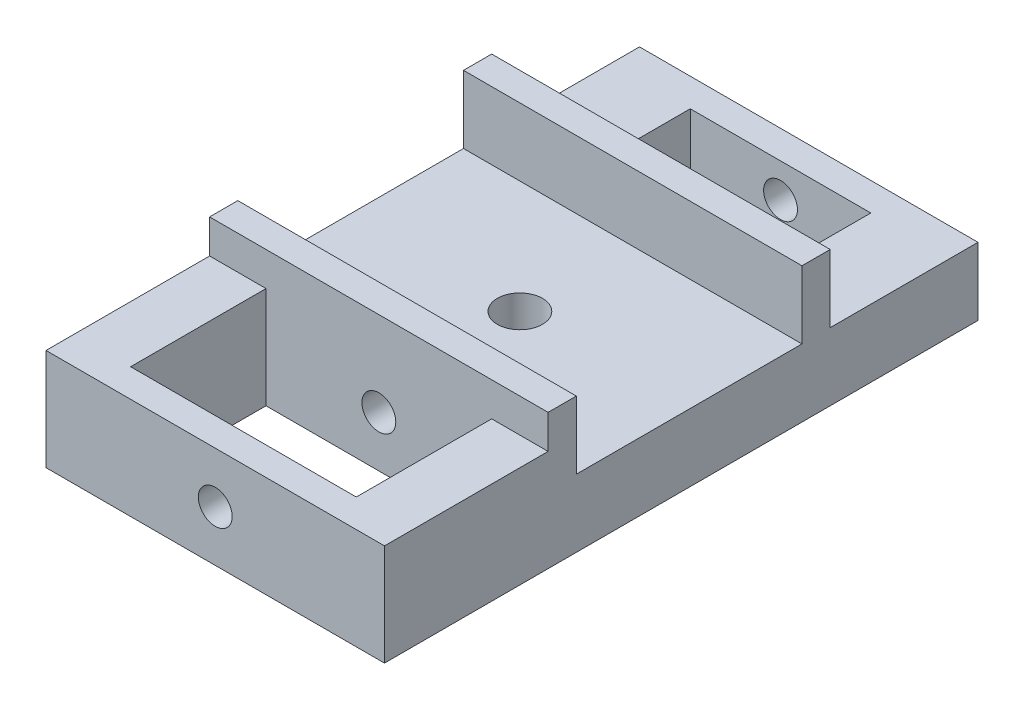
SolidWorks part; units mm, degrees
ref_plane "Front" through (0, 0, 0) normal (0, 0, 1) x (1, 0, 0)
ref_plane "Top" through (0, 0, 0) normal (0, 1, 0) x (1, 0, 0)
ref_plane "Right" through (0, 0, 0) normal (1, 0, 0) x (0, 0, -1)
sketch "Sketch1" plane through (0, 0, 0) normal (0, 1, 0) x (1, 0, 0)
  line L0 (0, -20) -> (0, -22.5)
  line L1 (0, 0) -> (-30, 0)
  line L2 (0, 0) -> (0, -20)
  line L3 (0, -20) -> (-30, -20)
  line L4 (-30, 0) -> (-30, -20)
  line L5 (0, -22.5) -> (-30, -22.5)
  line L6 (-30, -22.5) -> (-30, -20)
  line L7 (0, 0) -> (-7, 0)
  line L8 (-30, 0) -> (0, 0)
  line L9 (-30, 0) -> (-30, 2.5)
  line L10 (-30, 2.5) -> (0, 2.5)
  line L11 (0, 0) -> (0, 2.5)
  line L12 (-30, 0) -> (-23, 0)
  line L13 (-30, 2.5) -> (-30, 13.1)
  line L14 (-30, 13.1) -> (0, 13.1)
  line L15 (0, 13.1) -> (0, 2.5)
  line L16 (0, 13.1) -> (0, 15.6)
  line L17 (0, 15.6) -> (-30, 15.6)
  line L18 (-30, 15.6) -> (-30, 13.1)
  line L19 (-7, 0) -> (-7, 15.6)
  line L20 (-23, 0) -> (-23, 15.6)
  dimension "D1" = 20
  dimension "D2" = 2.5
  dimension "D3" = 2.5
  dimension "D4" = 30
  dimension "D5" = 7
  dimension "D6" = 7
  dimension "D7" = 10.6
  dimension "D8" = 2.5
extrude "Boss-Extrude1" add sketch "Sketch1" along normal blind 6 contours L1 L8 L4 L3 L2 | L6 L5 L0 L3 | L20 L1 L19 L10 | L19 L1 L11 L10 | L19 L10 L15 L14 | L19 L14 L16 L17 | L20 L14 L19 L17 | L14 L20 L17 L18 | L10 L20 L14 L13 | L8 L20 L10 L9 region at (-15, 0, 10) region at (-15, 0, 21.25) region at (-3.5, 0, -1.25) region at (-15, 0, -1.25) region at (-3.5, 0, -7.8) region at (-26.5, 0, -1.25) region at (-3.5, 0, -14.35) region at (-26.5, 0, -7.8) region at (-15, 0, -14.35) region at (-26.5, 0, -14.35)
extrude "Boss-Extrude2" add sketch "Sketch1<3>" along normal blind 12 contours L19 L1 L11 L10 | L20 L1 L19 L10 | L6 L5 L0 L3 | L8 L20 L10 L9 region at (-15, 0, 21.25) region at (-3.5, 0, -1.25) region at (-15, 0, -1.25) region at (-26.5, 0, -1.25)
sketch "Sketch1<3>" plane through (0, 0, 0) normal (0, 1, 0) x (1, 0, 0) same geometry as "Sketch1"
sketch "Sketch3" plane through (0, 0, -15.6) normal (0, 0, -1) x (-1, 0, 0)
  line L0 (30, 3) -> (23, 3)
  line L1 (30, 6) -> (30, 0) construction
  line L2 (23, 3) -> (15, 3)
  circle A0 centre (15, 3) radius 1.5
  dimension "D1" = 7
  dimension "D2" = 8
extrude "Cut-Extrude2" cut sketch "Sketch3" against normal blind 16 contours A0
ref_plane "Plane1" through (0, 0, 10) normal (0, 0, -1) x (-1, 0, 0)
sketch "Sketch2" plane through (0, 6, 0) normal (0, 1, 0) x (1, 0, 0)
  line L0 (-30, -10) -> (0, -10)
  line L1 (-30, 0) -> (-30, -20) construction
  line L2 (0, 0) -> (0, -20) construction
  circle A0 centre (-15, -10) radius 2
extrude "Cut-Extrude1" cut sketch "Sketch2" against normal through all contours L0 A0 | L0 A0 region at (-15, 6, 9.1512) region at (-15, 6, 10.8488)
sketch "Sketch5" plane through (0, 0, 0) normal (0, -1, 0) x (1, 0, 0)
  line L0 (-30, 22.5) -> (-25, 22.5)
  line L1 (-30, 22.5) -> (0, 22.5)
  line L2 (-30, 22.5) -> (-30, 34.5)
  line L3 (0, 22.5) -> (0, 34.5)
  line L4 (-30, 34.5) -> (0, 34.5)
  line L5 (-25, 22.5) -> (-25, 34.5)
  line L6 (-25, 34.5) -> (-5, 34.5)
  line L7 (-5, 34.5) -> (-5, 22.5)
  line L8 (-5, 22.5) -> (0, 22.5)
  line L9 (-30, 34.5) -> (-30, 37)
  line L10 (-30, 37) -> (0, 37)
  line L11 (0, 37) -> (0, 34.5)
  line M7 (0, 22.5) -> (-30, 22.5)
  dimension "D1" = 12
  dimension "D2" = 5
  dimension "D3" = 5
  dimension "D4" = 2.5
extrude "Boss-Extrude3" add sketch "Sketch5" against normal blind 9 contours L5 L4 L2 M7 | L11 L10 L9 L4 | L4 L7 L3 M7 region at (-27.5, 0, 28.5) region at (-15, 0, 35.75) region at (-2.5, 0, 28.5)
sketch "Sketch6" plane through (0, 0, 37) normal (0, 0, 1) x (1, 0, 0)
  line L0 (-30, 0) -> (0, 0) construction
  line L3 (0, 4.5) -> (-15, 4.5)
  circle A1 centre (-15, 4.5) radius 1.5
  dimension "D1" = 4.5
extrude "Cut-Extrude4" cut sketch "Sketch6" against normal blind 16.99 contours A1
